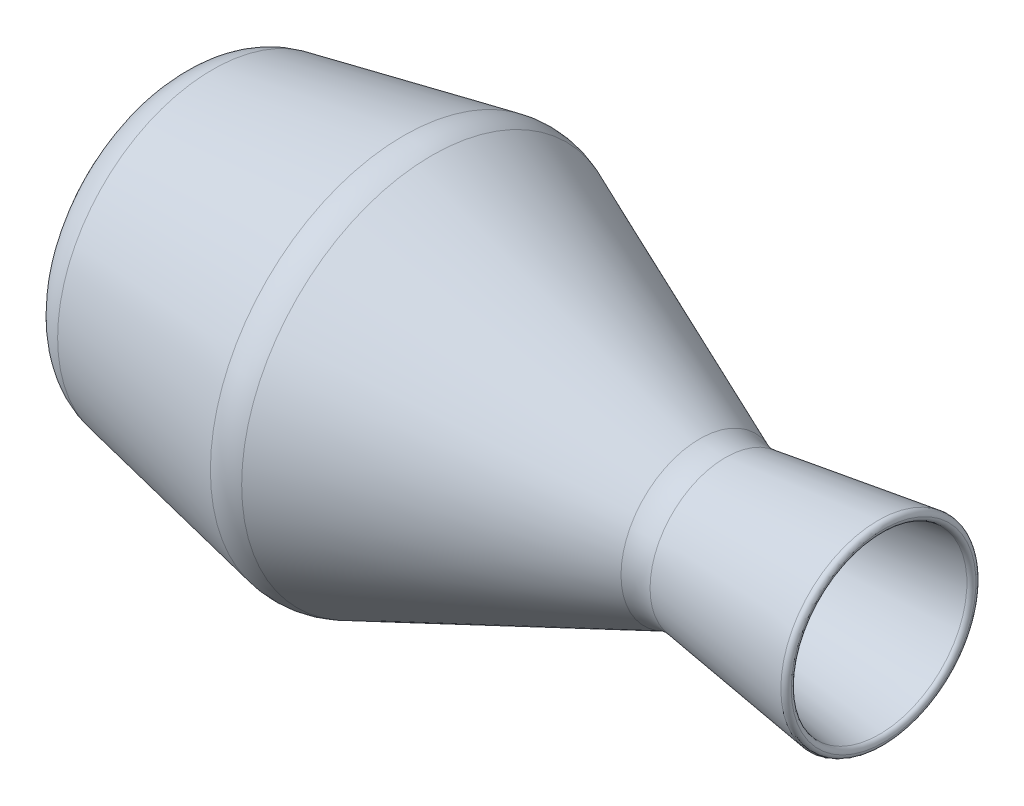
SolidWorks part; units mm, degrees
ref_plane "정면" through (0, 0, 0) normal (0, 0, 1) x (1, 0, 0)
ref_plane "윗면" through (0, 0, 0) normal (0, 1, 0) x (1, 0, 0)
ref_plane "우측면" through (0, 0, 0) normal (1, 0, 0) x (0, 0, -1)
sketch "스케치2" plane through (0, 0, 0) normal (0, 1, 0) x (1, 0, 0)
  line L0 (-92.1849, 4.5831) -> (133.8252, 4.5831) construction
  line L1 (-78.8285, 4.5831) -> (-78.8285, 34.5831)
  line L4 (-28.8285, 44.5831) -> (-78.8285, 34.5831)
  line L8 (31.1715, 19.5831) -> (-28.8285, 44.5831)
  line L10 (66.1715, 24.5831) -> (31.1715, 19.5831)
  line L11 (66.1715, 24.5831) -> (66.1715, 22.5627)
  line L15 (-76.8285, 4.5831) -> (-76.8285, 32.9434)
  line L16 (-29.0346, 42.5022) -> (-76.8285, 32.9434)
  line L17 (30.9099, 17.5254) -> (-29.0346, 42.5022)
  line L18 (64.1715, 22.277) -> (30.9099, 17.5254)
  line L19 (64.1715, 22.277) -> (66.1715, 22.5627)
  line L20 (-78.8285, 4.5831) -> (-76.8285, 4.5831)
  line L22 (66.1715, 24.5831) -> (66.1715, -15.4169) construction
  line L23 (64.1715, 22.277) -> (64.1715, -13.1109) construction
  line L25 (-76.8285, -23.7773) -> (-76.8285, 32.9434) construction
  line L26 (-78.8285, -25.4169) -> (-78.8285, 34.5831) construction
  line L27 (-29.0346, -33.3361) -> (-76.8285, -23.7773) construction
  line L28 (-28.8285, -35.4169) -> (-78.8285, -25.4169) construction
  line L29 (31.1715, -10.4169) -> (-28.8285, -35.4169) construction
  line L30 (30.9099, -8.3593) -> (-29.0346, -33.3361) construction
  line L31 (64.1715, -13.1109) -> (30.9099, -8.3593) construction
  line L32 (66.1715, -15.4169) -> (31.1715, -10.4169) construction
  point P5 (66.1715, 4.5831)
  point P12 (-78.8285, 19.5831)
revolve "회전5" add sketch "스케치2" angle 360 about L0
fillet "필렛1" radius 1 2 edges at (66.1715, 0, 13.3966) (66.1715, 0, 15.4169)
fillet "필렛4" radius 10 6 edges at (-78.8285, 0, 25.4169) (-29.0346, 0, 33.3361) (-76.8285, 0, 23.7773) (31.1715, 0, 10.4169) (30.9099, 0, 8.3593) (-28.8285, 0, 35.4169)
